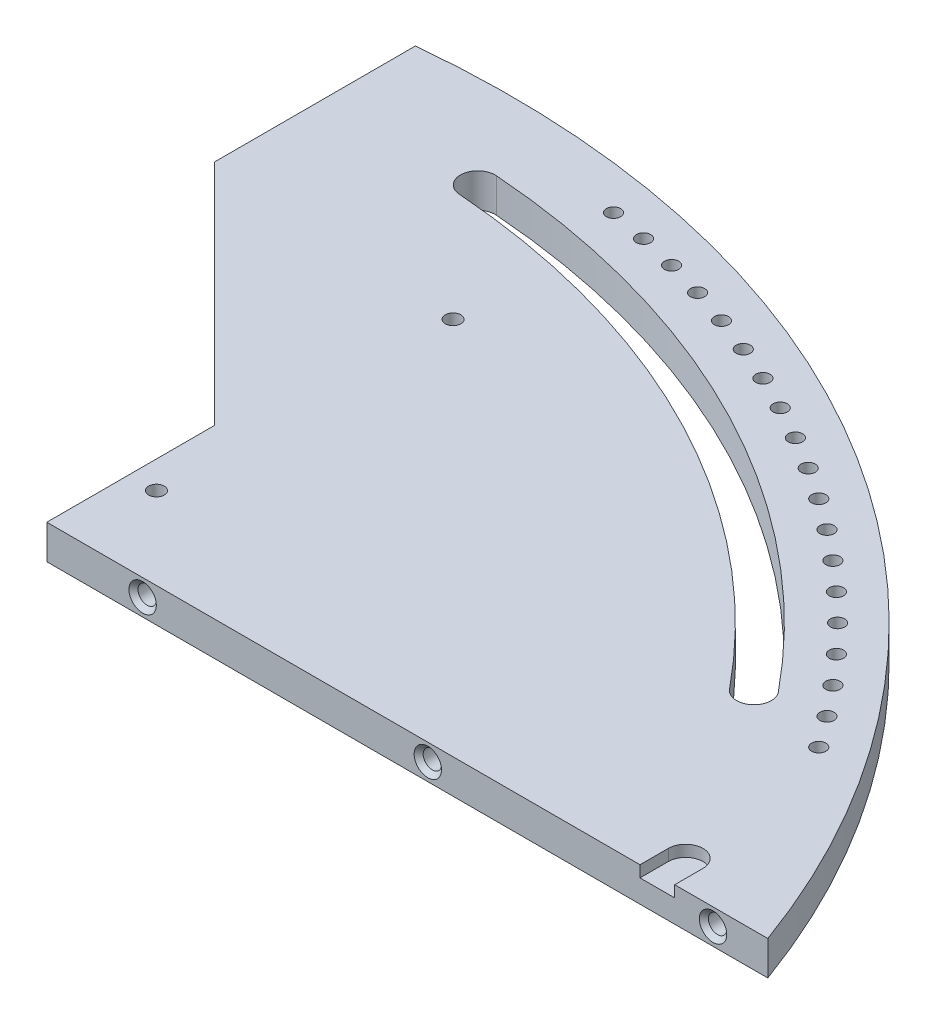
SolidWorks part; units mm, degrees
ref_plane "Front Plane" through (0, 0, 0) normal (0, 0, 1) x (1, 0, 0)
ref_plane "Top Plane" through (0, 0, 0) normal (0, 1, 0) x (1, 0, 0)
ref_plane "Right Plane" through (0, 0, 0) normal (1, 0, 0) x (0, 0, -1)
sketch "Sketch1" plane through (0, 0, 0) normal (0, 1, 0) x (1, 0, 0)
  line L4 (0, 277.4452) -> (0, 0) construction
  line L5 (0, 0) -> (355.6243, 0) construction
  line L6 (-154.5506, 254) -> (355.6243, 254) construction
  line L7 (38.1, 86.6583) -> (238.76, 86.6583)
  line L8 (-25.4, 252.7268) -> (-25.4, 196.85)
  line L9 (-25.4, 196.85) -> (38.1, 133.35)
  line L10 (38.1, 133.35) -> (38.1, 86.6583)
  arc A0 (238.76, 86.6583) -> (-25.4, 252.7268) centre (0, 0) ccw
  point P8 (0, 0)
  point P12 (0, 0)
  dimension "D6" = 254
  dimension "D1" = 254
  dimension "D2" = 200.66
  dimension "D3" = 133.35
  dimension "D4" = 63.5
  dimension "D5" = 38.1
  dimension "D7" = 196.85
extrude "Boss-Extrude1" add sketch "Sketch1" along normal mid plane 9.525 contours L10 L7 A0 L8 L9
sketch "Sketch2" plane through (0, 4.7625, 0) normal (0, 1, 0) x (1, 0, 0)
  line L0 (0, 0) -> (0, 358.0939) construction
  line L1 (0, 0) -> (18.9515, 361.616) construction
  line L2 (0, 0) -> (313.3603, 244.8239) construction
  arc A0 (180.8272, 147.5313) -> (17.1323, 232.7455) centre (0, 0) ccw
  arc A1 (173.3485, 141.4297) -> (16.4238, 223.1195) centre (0, 0) ccw
  arc A2 (17.1323, 232.7455) -> (16.4238, 223.1195) centre (16.7781, 227.9325) ccw
  arc A3 (173.3485, 141.4297) -> (180.8272, 147.5313) centre (177.0879, 144.4805) ccw
  circle A4 centre (0, 0) radius 233.3752 construction
  circle A5 centre (0, 0) radius 223.7232 construction
  dimension "D3" = 466.7504
  dimension "D1" = 3
  dimension "D2" = 52
  dimension "D4" = 9.652
extrude "Cut-Extrude2" cut sketch "Sketch2" against normal through all contours A1 A2 A0 A3
sketch "Sketch3" plane through (0, -4.7625, 0) normal (0, -1, 0) x (1, 0, 0)
  line L0 (0, 0) -> (0, -356.4914) construction
  line L1 (0, 0) -> (62.6758, -355.4523) construction
  line L6 (38.1, -133.35) -> (-25.4, -196.85)
  line L7 (-25.4, -196.85) -> (-25.4, -252.7268)
  line L8 (238.76, -86.6583) -> (38.1, -86.6583)
  line L9 (38.1, -86.6583) -> (38.1, -133.35)
  line L10 (38.1, -133.35) -> (-25.4, -196.85) construction
  line L11 (-25.4, -196.85) -> (-25.4, -252.7268) construction
  line L12 (238.76, -86.6583) -> (38.1, -86.6583) construction
  line L13 (38.1, -86.6583) -> (38.1, -133.35) construction
  arc A0 (-25.4, -242.5135) -> (227.9217, -86.6583) centre (0, 0) ccw construction
  arc A2 (-25.4, -252.7268) -> (238.76, -86.6583) centre (0, 0) ccw
  arc A3 (-25.4, -252.7268) -> (238.76, -86.6583) centre (0, 0) ccw construction
  point P3 (0, 0)
  point P12 (0, 0)
  dimension "D3" = 243.84
  dimension "D1" = 10
  dimension "D2" = 0
hole_wizard "CSK for M5 Cross Recess Flat Head Screw1" positions "Sketch4" profile "Sketch5" countersink size "M5" standard "IS" end condition up to next
sketch "Sketch4" plane through (0, -4.7625, 0) normal (0, -1, 0) x (-1, 0, 0)
  line L0 (0, 0) -> (-62.6758, 355.4523) construction
  arc A0 (25.4, 242.5135) -> (-227.9217, 86.6583) centre (0, 0) ccw construction
  point P0 (-42.3424, 240.1355)
sketch "Sketch5" plane through (42.3424, -4.7625, -240.1355) normal (1, 0, 0) x (0, 0, -1)
  line L0 (0, 0) -> (0, 9.525)
  line L1 (0, 9.525) -> (1.9812, 9.525)
  line L2 (1.9812, 9.525) -> (1.9812, 2.0677)
  line L3 (1.9812, 2.0677) -> (3.175, 0)
  line L5 (3.175, 0) -> (0, 0)
  line L6 (-1.9812, 2.0677) -> (-3.175, 0) construction
  line L11 (0, -6.35) -> (0, 107.95) construction
  dimension "Thru Hole Dia." = 3.9624
  dimension "Thru Hole Depth" = 9.525
  dimension "Near C'Sink Dia." = 6.35
  dimension "Near C'Sink Angle" = 60
ref_axis "Axis1" through (0, -329.9399, 0) along (0, 1, 0)
pattern_circular "CirPattern1" count 19 every 2.5 about axis through (0, -329.9399, 0) along (0, 1, 0) of "CSK for M5 Cross Recess Flat Head Screw1" reverse direction yes
hole_wizard "CBORE for M5 Cross Recess Pan Head Screw2" positions "Sketch8" profile "Sketch9" counterbore size "M5" standard "IS" end condition through all
sketch "Sketch8" plane through (0, -4.7625, 0) normal (0, -1, 0) x (-1, 0, 0)
  line L0 (-38.1, 86.6583) -> (-38.1, 133.35) construction
  point P0 (-45.72, 192.1002)
  point P2 (-45.72, 109.5502)
  point P6 (0, 0)
  dimension "D1" = 109.5502
  dimension "D2" = 192.1002
  dimension "D3" = 7.62
sketch "Sketch9" plane through (45.72, -4.7625, -192.1002) normal (1, 0, 0) x (0, 0, -1)
  line L0 (0, 0) -> (0, 9.525)
  line L1 (0, 9.525) -> (2.1717, 9.525)
  line L3 (2.1717, 9.525) -> (2.1717, 4.1656)
  line L4 (2.1717, 4.1656) -> (3.9751, 4.1656)
  line L5 (3.9751, 4.1656) -> (3.9751, 0)
  line L7 (3.9751, 0) -> (0, 0)
  line L11 (0, -6.35) -> (0, 107.95) construction
  dimension "Thru Hole Dia." = 4.3434
  dimension "Thru Hole Depth" = 9.525
  dimension "C'Bore Dia." = 7.9502
  dimension "C'Bore Depth" = 4.1656
sketch "Sketch10" plane through (0, 4.7625, 0) normal (0, 1, 0) x (1, 0, 0)
  line L0 (203.2, 94.5323) -> (203.2, 86.6583)
  line L1 (238.76, 86.6583) -> (38.1, 86.6583) construction
  line L2 (212.852, 94.5323) -> (212.852, 86.6583)
  line L3 (38.1, 86.6583) -> (38.1, 133.35) construction
  line L4 (203.2, 86.6583) -> (212.852, 86.6583)
  arc A0 (212.852, 94.5323) -> (203.2, 94.5323) centre (208.026, 94.5323) ccw
  point P8 (203.2, 90.5953)
  dimension "D1" = 9.652
  dimension "D2" = 12.7
  dimension "D3" = 165.1
extrude "Cut-Extrude5" cut sketch "Sketch10" against normal blind 3.175
hole_wizard "1/4-20 Tapped Hole1" positions "Sketch11" profile "Sketch12" tap size "1/4-20" standard "ANSI Inch"
sketch "Sketch11" plane through (0, 0, -86.6583) normal (0, 0, 1) x (1, 0, 0)
  line L0 (-25.4, 4.7625) -> (-25.4, -4.7625) construction
  point P0 (64.77, 0)
  point P2 (144.145, 0)
  point P4 (223.52, 0)
  point P7 (0, 0)
  dimension "D1" = 90.17
  dimension "D2" = 169.545
  dimension "D3" = 248.92
sketch "Sketch12" plane through (64.77, 0, -86.6583) normal (1, 0, 0) x (0, -1, 0)
  line L0 (0, 0) -> (0, 20.5838)
  line L1 (0, 20.5838) -> (2.5527, 19.05)
  line L2 (2.5527, 19.05) -> (2.5527, 1.2573)
  line L3 (2.5527, 1.2573) -> (3.81, 0)
  line L5 (3.81, 0) -> (0, 0)
  line L6 (-2.5527, 1.2573) -> (-3.81, 0) construction
  line L10 (0, 20.5838) -> (-2.5527, 19.05) construction
  line L11 (0, -6.35) -> (0, 107.95) construction
  dimension "Tap Drill Dia." = 5.1054
  dimension "Tap Drill Depth" = 19.05
  dimension "Near C'Sink Dia." = 7.62
  dimension "Near C'Sink Angle" = 90
  dimension "Drill Angle" = 118
cosmetic thread "Hole Thread1" parameters "D1"=12.7, "D2"=6.35
cosmetic thread "Hole Thread2" parameters "D1"=12.7, "D2"=6.35
cosmetic thread "Hole Thread3" parameters "D1"=12.7, "D2"=6.35
